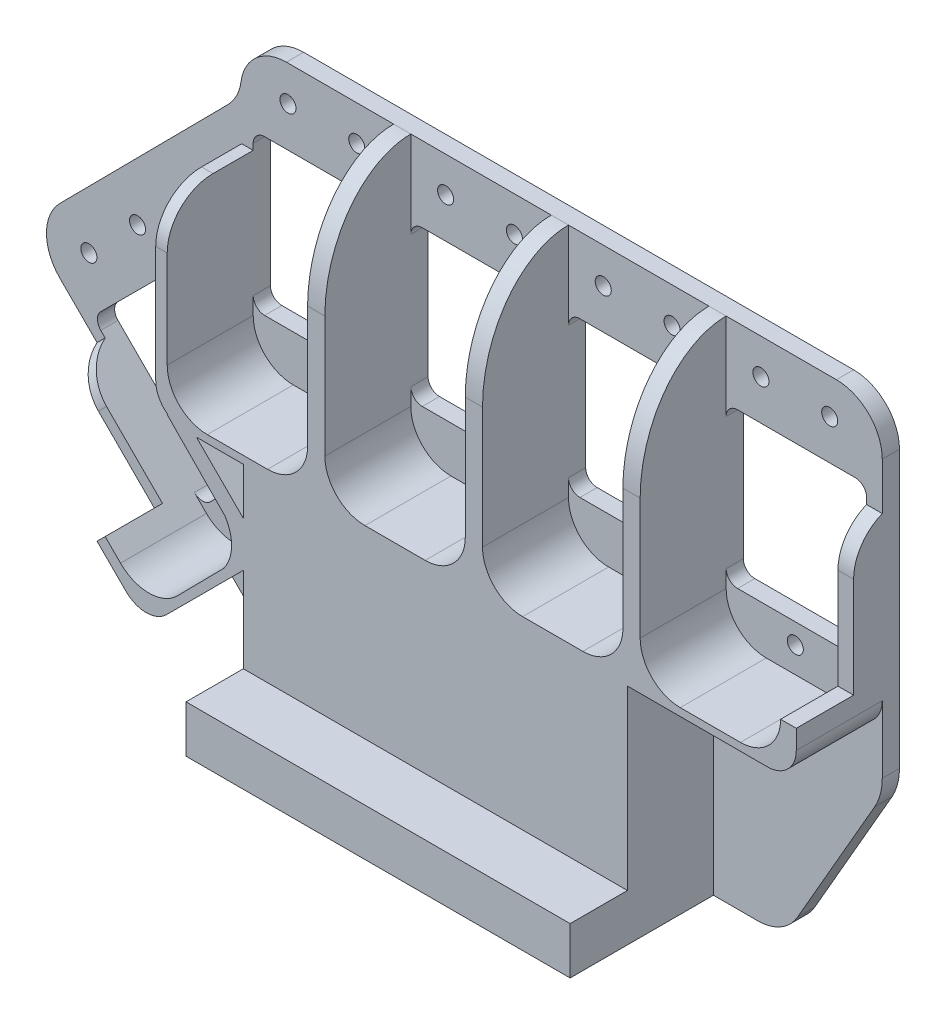
SolidWorks part; units mm, degrees
ref_plane "前视基准面" through (0, 0, 0) normal (0, 0, 1) x (1, 0, 0)
ref_plane "上视基准面" through (0, 0, 0) normal (0, 1, 0) x (1, 0, 0)
ref_plane "右视基准面" through (0, 0, 0) normal (1, 0, 0) x (0, 0, -1)
other "Configuration Table"
sketch "草图2" plane through (0, 0, 0) normal (0, 0, 1) x (1, 0, 0)
  line L0 (151.0633, 209.0132) -> (151.0476, 168.4956)
  line L1 (178.2976, 201.2948) -> (178.2976, 178.2948)
  line L2 (178.2976, 178.2948) -> (178.2976, 175.2948)
  line L3 (206.1919, 197.3972) -> (206.1919, 171.3972)
  line L4 (194.4691, 218.3694) -> (201.3108, 217.5164)
  line L5 (201.3108, 217.5164) -> (208.7441, 216.356)
  line L6 (166.5748, 222.2669) -> (173.4165, 221.4139)
  line L261 (199.1919, 164.3972) -> (192.9419, 164.3972)
  line L262 (237.2256, 158.3592) -> (242.1719, 178.962)
  line L263 (236.0401, 178.625) -> (234.6391, 165.2957)
  line L264 (225.8467, 158.1757) -> (217.3932, 159.0642)
  line L266 (210.2733, 167.8566) -> (212.2453, 186.6193)
  line L267 (252.608, 147.4673) -> (245.8094, 149.0995)
  line L268 (263.7227, 151.9978) -> (271.0421, 182.4855)
  line L269 (188.6919, 164.3972) -> (192.9419, 164.3972)
  line L270 (265.6404, 180.333) -> (245.7068, 185.1186)
  line L271 (252.8645, 197.798) -> (254.0666, 202.8051)
  line L272 (265.506, 196.9076) -> (265.0192, 194.88)
  line L273 (242.1719, 178.962) -> (243.2952, 183.6408)
  line L274 (187.6765, 215.8498) -> (187.692, 213.3583)
  line L275 (200.1917, 213.4362) -> (200.1725, 216.5198)
  line L276 (183.6919, 199.3972) -> (204.1919, 199.3972)
  line L278 (212.2623, 167.6475) -> (232.65, 165.5047)
  line L279 (220.5261, 208.0048) -> (221.0496, 212.986)
  line L280 (235.4723, 192.3568) -> (215.0846, 194.4996)
  line L281 (233.2553, 209.5307) -> (232.9576, 206.6982)
  line L282 (236.0401, 178.625) -> (237.2523, 190.1587)
  line L283 (212.8865, 192.7196) -> (212.2453, 186.6193)
  line L284 (183.6919, 172.3972) -> (204.1919, 172.3972)
  line L285 (239.4038, 158.8646) -> (259.3374, 154.079)
  line L286 (262.7567, 147.974) -> (251.8225, 127.8461)
  line L287 (263.7227, 151.9978) -> (262.7567, 147.974)
  line L288 (181.6919, 197.3972) -> (181.6919, 174.3972)
  line L289 (181.6919, 171.3972) -> (181.6919, 174.3972)
  line L290 (267.1183, 177.9214) -> (261.0487, 152.6398)
  line L291 (171.2976, 168.2948) -> (165.0476, 168.2948)
  line L293 (160.7976, 168.2948) -> (165.0476, 168.2948)
  line L295 (159.7822, 219.7473) -> (159.7977, 217.2558)
  line L296 (172.2974, 217.3337) -> (172.2782, 220.4173)
  line L297 (155.7976, 203.2948) -> (176.2976, 203.2948)
  line L300 (155.7976, 176.2948) -> (176.2976, 176.2948)
  line L301 (153.7976, 201.2948) -> (153.7976, 178.2948)
  line L302 (153.7976, 175.2948) -> (153.7976, 178.2948)
  line L303 (173.4165, 221.4139) -> (194.4691, 218.3694)
  line L304 (187.6765, 215.8498) -> (187.6765, 218.2449)
  line L305 (187.6765, 218.2449) -> (186.8438, 219.4721)
  line L306 (234.2789, 127.8461) -> (251.8225, 127.8461)
  line L307 (233.4789, 133.8446) -> (233.4789, 127.8461)
  line L308 (233.4789, 127.8461) -> (234.2789, 127.8461)
  line L309 (178.4789, 128.6348) -> (178.4789, 135.1402)
  line L310 (172.4789, 127.8461) -> (173.1594, 127.8461)
  line L311 (178.4789, 127.8461) -> (178.4789, 128.6348)
  line L312 (177.6789, 127.8461) -> (178.4789, 127.8461)
  line L313 (173.1594, 127.8461) -> (177.6789, 127.8461)
  line L314 (233.4789, 143.0663) -> (233.4789, 140.4276)
  line L315 (178.4789, 135.1402) -> (178.4789, 139.2823)
  line L316 (178.4789, 139.2823) -> (178.4789, 146.9191)
  line L317 (178.4789, 146.9191) -> (178.4789, 157.8461)
  line L318 (199.0973, 156.1096) -> (218.0428, 154.1184)
  line L319 (181.4789, 160.8461) -> (190.8607, 160.8461)
  line L320 (151.0476, 168.4956) -> (172.4789, 127.8461)
  arc A276 (237.2256, 158.3592) -> (238.6979, 152.1924) centre (244.0322, 156.725) ccw
  arc A277 (210.2733, 167.8566) -> (217.3932, 159.0642) centre (218.2295, 167.0204) ccw
  arc A278 (199.1919, 164.3972) -> (206.1919, 171.3972) centre (199.1919, 171.3972) ccw
  arc A279 (225.8467, 158.1757) -> (234.6391, 165.2957) centre (226.6829, 166.1319) ccw
  arc A281 (242.1719, 178.962) -> (242.2118, 179.1563) centre (239.2548, 179.6624) ccw
  arc A282 (212.2453, 186.6193) -> (212.2566, 186.7575) centre (209.2618, 186.9329) ccw
  arc A283 (236.0666, 178.8175) -> (236.0401, 178.625) centre (239.0236, 178.3114) ccw
  arc A284 (246.0441, 206.6986) -> (242.0035, 208.0676) centre (168.9419, -14.234) ccw
  arc A285 (220.2745, 214.0661) -> (208.7441, 216.356) centre (168.9419, -14.234) ccw
  arc A286 (252.608, 147.4673) -> (261.0487, 152.6398) centre (254.2421, 154.2739) ccw
  arc A287 (181.6919, 171.3972) -> (188.6919, 164.3972) centre (188.6919, 171.3972) ccw
  circle A288 centre (251.4735, 190.9331) radius 1.4
  circle A289 centre (263.142, 188.1317) radius 1.4
  arc A290 (267.1183, 177.9214) -> (265.6404, 180.333) centre (265.1735, 178.3883) ccw
  arc A291 (245.7068, 185.1186) -> (243.2952, 183.6408) centre (245.2399, 183.1739) ccw
  arc A292 (254.0666, 202.8051) -> (253.4554, 203.971) centre (253.0943, 203.0385) ccw
  arc A293 (252.8645, 197.798) -> (265.0192, 194.88) centre (258.9419, 196.339) ccw
  arc A294 (267.1505, 197.4145) -> (265.506, 196.9076) centre (266.4783, 196.6741) ccw
  arc A295 (253.4554, 203.971) -> (246.0441, 206.6986) centre (168.9419, -14.234) ccw
  arc A296 (271.7032, 188.063) -> (267.1505, 197.4145) centre (257.74, 187.0491) ccw
  arc A297 (187.692, 213.3583) -> (200.1917, 213.4362) centre (193.9419, 213.3972) ccw
  arc A298 (201.3108, 217.5164) -> (200.1725, 216.5198) centre (201.1725, 216.526) ccw
  arc A299 (206.1919, 197.3972) -> (204.1919, 199.3972) centre (204.1919, 197.3972) ccw
  arc A300 (183.6919, 199.3972) -> (181.6919, 197.3972) centre (183.6919, 197.3972) ccw
  circle A301 centre (199.9419, 206.3972) radius 1.4
  circle A302 centre (187.9419, 206.3972) radius 1.4
  arc A304 (210.4824, 169.8456) -> (212.2623, 167.6475) centre (212.4714, 169.6366) ccw
  arc A305 (232.65, 165.5047) -> (234.8481, 167.2847) centre (232.8591, 167.4938) ccw
  circle A306 centre (222.0903, 163.0953) radius 1.4
  arc A307 (220.5261, 208.0048) -> (232.9576, 206.6982) centre (226.7419, 207.3515) ccw
  circle A308 centre (220.043, 201.017) radius 1.4
  circle A309 centre (231.9773, 199.7627) radius 1.4
  arc A310 (237.2523, 190.1587) -> (235.4723, 192.3568) centre (235.2632, 190.3678) ccw
  arc A311 (221.0496, 212.986) -> (220.2745, 214.0661) centre (220.0551, 213.0905) ccw
  arc A312 (234.5301, 210.386) -> (233.2553, 209.5307) centre (234.2498, 209.4261) ccw
  arc A313 (215.0846, 194.4996) -> (212.8865, 192.7196) centre (214.8756, 192.5106) ccw
  arc A314 (242.0038, 208.0674) -> (234.5301, 210.386) centre (168.9419, -14.234) ccw
  arc A315 (204.1919, 172.3972) -> (206.1919, 174.3972) centre (204.1919, 174.3972) ccw
  circle A316 centre (193.9419, 168.8972) radius 1.4
  arc A317 (181.6919, 174.3972) -> (183.6919, 172.3972) centre (183.6919, 174.3972) ccw
  arc A318 (259.3374, 154.079) -> (261.749, 155.5569) centre (259.8043, 156.0238) ccw
  arc A319 (237.926, 161.2763) -> (239.4038, 158.8646) centre (239.8707, 160.8094) ccw
  circle A320 centre (248.5535, 153.0685) radius 1.4
  circle A321 centre (193.9419, 213.3972) radius 3.5
  circle A323 centre (258.9419, 196.339) radius 3.5
  arc A324 (263.3908, 199.858) -> (253.4554, 203.971) centre (168.9419, -14.234) ccw
  arc A325 (267.1505, 197.4145) -> (263.3908, 199.858) centre (257.74, 187.0491) ccw
  circle A326 centre (226.7419, 207.3515) radius 3.5
  arc A327 (234.5301, 210.386) -> (220.2745, 214.0661) centre (168.9419, -14.234) ccw
  arc A328 (171.2976, 168.2948) -> (178.2976, 175.2948) centre (171.2976, 175.2948) ccw
  arc A331 (153.7976, 175.2948) -> (160.7976, 168.2948) centre (160.7976, 175.2948) ccw
  arc A332 (159.7822, 219.7473) -> (158.3002, 220.6173) centre (158.7822, 219.7411) ccw
  arc A333 (159.7977, 217.2558) -> (172.2974, 217.3337) centre (166.0476, 217.2948) ccw
  arc A334 (173.4165, 221.4139) -> (172.2782, 220.4173) centre (173.2782, 220.4235) ccw
  arc A335 (178.2976, 201.2948) -> (176.2976, 203.2948) centre (176.2976, 201.2948) ccw
  arc A336 (155.7976, 203.2948) -> (153.7976, 201.2948) centre (155.7976, 201.2948) ccw
  circle A337 centre (172.0476, 210.2948) radius 1.4
  circle A338 centre (160.0476, 210.2948) radius 1.4
  arc A339 (158.3002, 220.6173) -> (152.4939, 214.5477) centre (165.0476, 208.3505) ccw
  arc A340 (176.2976, 176.2948) -> (178.2976, 178.2948) centre (176.2976, 178.2948) ccw
  circle A341 centre (166.0476, 172.7948) radius 1.4
  arc A342 (153.7976, 178.2948) -> (155.7976, 176.2948) centre (155.7976, 178.2948) ccw
  circle A343 centre (166.0476, 217.2948) radius 3.5
  arc A345 (166.5748, 222.2669) -> (158.3002, 220.6173) centre (165.0476, 208.3505) ccw
  arc A346 (220.5415, 152.1792) -> (221.76, 150.0096) centre (228.0411, 154.9641) ccw
  arc A347 (193.3351, 159.5424) -> (199.0973, 156.1096) centre (199.9335, 164.0658) ccw
  arc A348 (220.5415, 152.1792) -> (218.0428, 154.1184) centre (217.7292, 151.1348) ccw
  arc A349 (193.3351, 159.5424) -> (190.8607, 160.8461) centre (190.8607, 157.8461) ccw
  arc A350 (181.4789, 160.8461) -> (178.4789, 157.8461) centre (181.4789, 157.8461) ccw
  spline S5 degree 3 poles (245.8094, 149.0995) (244.7023, 149.3653) (243.562, 149.639) (242.3981, 149.9185) knots 0 0 0 0 1 1 1 1
  spline S6 degree 3 poles (242.3981, 149.9185) (240.9661, 150.2604) (239.6561, 151.0615) (238.6979, 152.1924) knots 0 0 0 0 1 1 1 1
  spline S7 degree 3 poles (271.0421, 182.4855) (271.1468, 182.9215) (271.2515, 183.3575) (271.3531, 183.7809) knots 0 0 0 0 1 1 1 1
  spline S8 degree 3 poles (271.3531, 183.7809) (271.6392, 184.9581) (271.73, 186.0745) (271.7435, 187.2429) (271.7328, 187.5457) (271.7129, 187.9558) (271.7023, 188.0633) (271.7026, 188.063) knots 0 0 0 0 0.5 0.5 0.75 0.75 1 1 1 1
  spline S9 degree 3 poles (152.4939, 214.5476) (152.4935, 214.5473) (152.4251, 214.4133) (152.183, 213.882) (152.0119, 213.4848) (151.6571, 212.4716) (151.4748, 211.8536) (151.1955, 210.4931) (151.098, 209.7566) (151.0633, 209.0132) knots 0 0 0 0 0.25 0.25 0.5 0.5 0.75 0.75 1 1 1 1
  spline S10 degree 3 poles (233.4789, 140.4276) (233.4789, 138.7088) (233.4789, 136.2853) (233.4789, 133.8446) knots 0 0 0 0 1 1 1 1
  spline S11 degree 3 poles (233.2337, 144.2542) (233.3952, 143.8804) (233.4792, 143.4735) (233.4789, 143.0663) knots 0 0 0 0 1 1 1 1
  spline S12 degree 3 poles (231.1793, 145.9834) (231.6902, 145.8625) (232.1463, 145.6054) (232.8415, 144.9724) (233.0819, 144.6067) (233.2337, 144.2542) knots 0 0 0 0 0.5 0.5 1 1 1 1
  spline S13 degree 3 poles (226.1736, 147.1852) (227.9043, 146.7697) (229.5835, 146.3665) (231.1793, 145.9834) knots 0 0 0 0 1 1 1 1
  spline S14 degree 3 poles (221.76, 150.0096) (222.8696, 148.5987) (224.4447, 147.5969) (226.1736, 147.1852) knots 0 0 0 0 1 1 1 1
  line B0 (187.9419, 206.3972) -> (187.9419, 208.8972)
  line B1 (187.9419, 206.3972) -> (185.4419, 206.3972)
  line B2 (187.9419, 206.3972) -> (187.9419, 203.8972)
  line B3 (187.9419, 206.3972) -> (190.4419, 206.3972)
  line B4 (187.9419, 208.8972) -> (187.9419, 210.2972)
  line B5 (185.4419, 206.3972) -> (184.0419, 206.3972)
  line B6 (187.9419, 203.8972) -> (187.9419, 202.4972)
  line B7 (190.4419, 206.3972) -> (191.8419, 206.3972)
  line B8 (222.0903, 163.0953) -> (222.0903, 165.5953)
  line B9 (222.0903, 163.0953) -> (219.5903, 163.0953)
  line B10 (222.0903, 163.0953) -> (222.0903, 160.5953)
  line B11 (222.0903, 163.0953) -> (224.5903, 163.0953)
  line B12 (222.0903, 165.5953) -> (222.0903, 166.9953)
  line B13 (219.5903, 163.0953) -> (218.1903, 163.0953)
  line B14 (222.0903, 160.5953) -> (222.0903, 159.1953)
  line B15 (224.5903, 163.0953) -> (225.9903, 163.0953)
  line B16 (251.4735, 190.9331) -> (251.4735, 193.4331)
  line B17 (251.4735, 190.9331) -> (248.9735, 190.9331)
  line B18 (251.4735, 190.9331) -> (251.4735, 188.4331)
  line B19 (251.4735, 190.9331) -> (253.9735, 190.9331)
  line B20 (251.4735, 193.4331) -> (251.4735, 194.8331)
  line B21 (248.9735, 190.9331) -> (247.5735, 190.9331)
  line B22 (251.4735, 188.4331) -> (251.4735, 187.0331)
  line B23 (253.9735, 190.9331) -> (255.3735, 190.9331)
  line B24 (263.142, 188.1317) -> (263.142, 190.6317)
  line B25 (263.142, 188.1317) -> (260.642, 188.1317)
  line B26 (263.142, 188.1317) -> (263.142, 185.6317)
  line B27 (263.142, 188.1317) -> (265.642, 188.1317)
  line B28 (263.142, 190.6317) -> (263.142, 192.0317)
  line B29 (260.642, 188.1317) -> (259.242, 188.1317)
  line B30 (263.142, 185.6317) -> (263.142, 184.2317)
  line B31 (265.642, 188.1317) -> (267.042, 188.1317)
  line B32 (248.5535, 153.0685) -> (248.5535, 155.5685)
  line B33 (248.5535, 153.0685) -> (246.0535, 153.0685)
  line B34 (248.5535, 153.0685) -> (248.5535, 150.5685)
  line B35 (248.5535, 153.0685) -> (251.0535, 153.0685)
  line B36 (248.5535, 155.5685) -> (248.5535, 156.9685)
  line B37 (246.0535, 153.0685) -> (244.6535, 153.0685)
  line B38 (248.5535, 150.5685) -> (248.5535, 149.1685)
  line B39 (251.0535, 153.0685) -> (252.4535, 153.0685)
  line B40 (231.9773, 199.7627) -> (231.9773, 202.2627)
  line B41 (231.9773, 199.7627) -> (229.4773, 199.7627)
  line B42 (231.9773, 199.7627) -> (231.9773, 197.2627)
  line B43 (231.9773, 199.7627) -> (234.4773, 199.7627)
  line B44 (231.9773, 202.2627) -> (231.9773, 203.6627)
  line B45 (229.4773, 199.7627) -> (228.0773, 199.7627)
  line B46 (231.9773, 197.2627) -> (231.9773, 195.8627)
  line B47 (234.4773, 199.7627) -> (235.8773, 199.7627)
  line B48 (220.043, 201.017) -> (220.043, 203.517)
  line B49 (220.043, 201.017) -> (217.543, 201.017)
  line B50 (220.043, 201.017) -> (220.043, 198.517)
  line B51 (220.043, 201.017) -> (222.543, 201.017)
  line B52 (220.043, 203.517) -> (220.043, 204.917)
  line B53 (217.543, 201.017) -> (216.143, 201.017)
  line B54 (220.043, 198.517) -> (220.043, 197.117)
  line B55 (222.543, 201.017) -> (223.943, 201.017)
  line B56 (193.9419, 168.8972) -> (193.9419, 171.3972)
  line B57 (193.9419, 168.8972) -> (191.4419, 168.8972)
  line B58 (193.9419, 168.8972) -> (193.9419, 166.3972)
  line B59 (193.9419, 168.8972) -> (196.4419, 168.8972)
  line B60 (193.9419, 171.3972) -> (193.9419, 172.7972)
  line B61 (191.4419, 168.8972) -> (190.0419, 168.8972)
  line B62 (193.9419, 166.3972) -> (193.9419, 164.9972)
  line B63 (196.4419, 168.8972) -> (197.8419, 168.8972)
  line B64 (199.9419, 206.3972) -> (199.9419, 208.8972)
  line B65 (199.9419, 206.3972) -> (197.4419, 206.3972)
  line B66 (199.9419, 206.3972) -> (199.9419, 203.8972)
  line B67 (199.9419, 206.3972) -> (202.4419, 206.3972)
  line B68 (199.9419, 208.8972) -> (199.9419, 210.2972)
  line B69 (197.4419, 206.3972) -> (196.0419, 206.3972)
  line B70 (199.9419, 203.8972) -> (199.9419, 202.4972)
  line B71 (202.4419, 206.3972) -> (203.8419, 206.3972)
  line B72 (160.0476, 210.2948) -> (160.0476, 212.7948)
  line B73 (160.0476, 210.2948) -> (157.5476, 210.2948)
  line B74 (160.0476, 210.2948) -> (160.0476, 207.7948)
  line B75 (160.0476, 210.2948) -> (162.5476, 210.2948)
  line B76 (160.0476, 212.7948) -> (160.0476, 214.1948)
  line B77 (157.5476, 210.2948) -> (156.1476, 210.2948)
  line B78 (160.0476, 207.7948) -> (160.0476, 206.3948)
  line B79 (162.5476, 210.2948) -> (163.9476, 210.2948)
  line B80 (166.0476, 172.7948) -> (166.0476, 175.2948)
  line B81 (166.0476, 172.7948) -> (163.5476, 172.7948)
  line B82 (166.0476, 172.7948) -> (166.0476, 170.2948)
  line B83 (166.0476, 172.7948) -> (168.5476, 172.7948)
  line B84 (166.0476, 175.2948) -> (166.0476, 176.6948)
  line B85 (163.5476, 172.7948) -> (162.1476, 172.7948)
  line B86 (166.0476, 170.2948) -> (166.0476, 168.8948)
  line B87 (168.5476, 172.7948) -> (169.9476, 172.7948)
  line B88 (172.0476, 210.2948) -> (172.0476, 212.7948)
  line B89 (172.0476, 210.2948) -> (169.5476, 210.2948)
  line B90 (172.0476, 210.2948) -> (172.0476, 207.7948)
  line B91 (172.0476, 210.2948) -> (174.5476, 210.2948)
  line B92 (172.0476, 212.7948) -> (172.0476, 214.1948)
  line B93 (169.5476, 210.2948) -> (168.1476, 210.2948)
  line B94 (172.0476, 207.7948) -> (172.0476, 206.3948)
  line B95 (174.5476, 210.2948) -> (175.9476, 210.2948)
sketch_block_instance "SW_CENTERMARKSYMBOL_3-1"
sketch_block "SW_CENTERMARKSYMBOL_3"
sketch_block_instance "SW_CENTERMARKSYMBOL_4-1"
sketch_block "SW_CENTERMARKSYMBOL_4"
sketch_block_instance "SW_CENTERMARKSYMBOL_5-1"
sketch_block "SW_CENTERMARKSYMBOL_5"
sketch_block_instance "SW_CENTERMARKSYMBOL_6-1"
sketch_block "SW_CENTERMARKSYMBOL_6"
sketch_block_instance "SW_CENTERMARKSYMBOL_7-1"
sketch_block "SW_CENTERMARKSYMBOL_7"
sketch_block_instance "SW_CENTERMARKSYMBOL_8-1"
sketch_block "SW_CENTERMARKSYMBOL_8"
sketch_block_instance "SW_CENTERMARKSYMBOL_9-1"
sketch_block "SW_CENTERMARKSYMBOL_9"
sketch_block_instance "SW_CENTERMARKSYMBOL_10-1"
sketch_block "SW_CENTERMARKSYMBOL_10"
sketch_block_instance "SW_CENTERMARKSYMBOL_11-1"
sketch_block "SW_CENTERMARKSYMBOL_11"
sketch_block_instance "SW_CENTERMARKSYMBOL_3-2"
sketch_block_instance "SW_CENTERMARKSYMBOL_10-2"
sketch_block_instance "SW_CENTERMARKSYMBOL_11-2"
ref_plane "基准面2" through (0, 0, 15.8251) normal (0, 0, 1) x (1, 0, 0)
sketch "草图12" plane through (0, 0, 15.8251) normal (0, 0, 1) x (1, 0, 0)
  line L2 (157.1388, 216.4507) -> (268.9252, 216.4507)
  line L5 (268.9252, 216.4507) -> (268.9252, 157.5622)
  line L9 (251.8225, 127.8461) -> (233.4789, 127.8461)
  line L10 (233.4789, 127.8461) -> (233.4789, 143.0663)
  line L12 (178.4789, 127.8461) -> (178.4789, 157.8461)
  line L13 (181.4789, 160.8461) -> (190.8607, 160.8461)
  line L14 (199.0973, 156.1096) -> (218.0428, 154.1184)
  line L15 (226.1736, 147.1852) -> (231.1793, 145.9834)
  line L23 (188.6945, 203.2948) -> (209.1945, 203.2948)
  line L24 (211.1945, 201.2948) -> (211.1945, 178.2948)
  line L25 (209.1945, 176.2948) -> (188.6945, 176.2948)
  line L26 (186.6945, 178.2948) -> (186.6945, 201.2948)
  line L27 (186.6945, 178.2948) -> (186.6945, 175.2948)
  line L28 (211.1945, 178.2948) -> (211.1945, 175.2948)
  line L29 (193.6945, 168.2948) -> (204.1945, 168.2948)
  line L30 (268.9252, 157.5622) -> (251.8225, 127.8461)
  line L51 (216.1945, 203.2948) -> (236.6945, 203.2948)
  line L52 (238.6945, 201.2948) -> (238.6945, 178.2948)
  line L53 (236.6945, 176.2948) -> (216.1945, 176.2948)
  line L54 (214.1945, 178.2948) -> (214.1945, 201.2948)
  line L55 (214.1945, 178.2948) -> (214.1945, 175.2948)
  line L56 (238.6945, 178.2948) -> (238.6945, 175.2948)
  line L57 (221.1945, 168.2948) -> (231.6945, 168.2948)
  line L60 (161.1945, 203.2948) -> (181.6945, 203.2948)
  line L61 (183.6945, 201.2948) -> (183.6945, 178.2948)
  line L62 (181.6945, 176.2948) -> (161.1945, 176.2948)
  line L63 (159.1945, 178.2948) -> (159.1945, 201.2948)
  line L64 (159.1945, 178.2948) -> (159.1945, 175.2948)
  line L65 (183.6945, 178.2948) -> (183.6945, 175.2948)
  line L66 (166.1945, 168.2948) -> (176.6945, 168.2948)
  line L69 (238.6945, 201.2948) -> (238.6945, 178.2948)
  line L70 (238.6945, 178.2948) -> (238.6945, 175.2948)
  line L72 (243.6945, 203.2948) -> (264.1945, 203.2948)
  line L73 (265.8853, 200.2265) -> (265.8853, 179.3631)
  line L74 (264.1945, 176.2948) -> (243.6945, 176.2948)
  line L75 (241.6945, 178.2948) -> (241.6945, 201.2948)
  line L76 (241.6945, 178.2948) -> (241.6945, 175.2948)
  line L77 (265.8853, 179.3631) -> (265.8853, 175.1696)
  line L78 (248.6945, 168.2948) -> (259.1917, 168.2948)
  line L83 (325.7181, 277.8251) -> (346.2181, 277.8251)
  line L84 (348.2181, 275.8251) -> (348.2181, 252.8251)
  line L85 (346.2181, 250.8251) -> (325.7181, 250.8251)
  line L86 (323.7181, 252.8251) -> (323.7181, 275.8251)
  line L87 (323.7181, 252.8251) -> (323.7181, 249.8251)
  line L88 (348.2181, 252.8251) -> (348.2181, 249.8251)
  line L89 (330.7181, 242.8251) -> (341.2181, 242.8251)
  line L91 (352.2181, 277.8251) -> (372.7181, 277.8251)
  line L92 (374.7181, 275.8251) -> (374.7181, 252.8251)
  line L93 (372.7181, 250.8251) -> (352.2181, 250.8251)
  line L94 (350.2181, 252.8251) -> (350.2181, 275.8251)
  line L95 (350.2181, 252.8251) -> (350.2181, 249.8251)
  line L96 (374.7181, 252.8251) -> (374.7181, 249.8251)
  line L97 (357.2181, 242.8251) -> (367.7181, 242.8251)
  line L98 (299.404, 277.8251) -> (319.904, 277.8251)
  line L100 (319.904, 250.8251) -> (299.404, 250.8251)
  line L101 (159.6321, 140.0993) -> (169.0726, 149.5397)
  line L102 (297.404, 252.8251) -> (297.404, 249.8251)
  line L103 (321.904, 252.8251) -> (321.904, 249.8251)
  line L104 (304.404, 242.8251) -> (314.904, 242.8251)
  line L106 (374.7181, 275.8251) -> (374.7181, 252.8251)
  line L107 (374.7181, 252.8251) -> (374.7181, 249.8251)
  line L108 (378.7181, 277.8251) -> (399.2181, 277.8251)
  line L109 (401.2181, 275.8251) -> (401.2181, 252.8251)
  line L110 (399.2181, 250.8251) -> (378.7181, 250.8251)
  line L111 (376.7181, 252.8251) -> (376.7181, 275.8251)
  line L112 (376.7181, 252.8251) -> (376.7181, 249.8251)
  line L113 (401.2181, 252.8251) -> (401.2181, 249.8251)
  line L114 (383.7181, 242.8251) -> (394.2181, 242.8251)
  line L115 (166.1991, 157.98) -> (151.7034, 143.4843)
  line L117 (132.6116, 162.5762) -> (147.1073, 177.0719)
  line L118 (149.9357, 177.0719) -> (166.1991, 160.8084)
  line L121 (119.8478, 169.6832) -> (161.6848, 127.8461)
  line L122 (161.6848, 127.8461) -> (178.4789, 127.8461)
  line L124 (151.0538, 141.3055) -> (132.6116, 159.7478)
  line L126 (157.1388, 207.3145) -> (157.1388, 216.4507)
  line L129 (168.3779, 158.6297) -> (166.1991, 160.8084)
  line L130 (154.0169, 144.2791) -> (154.0432, 144.2528)
  line L131 (119.8478, 169.6832) -> (157.1388, 207.3145)
  line L132 (150.158, 176.8496) -> (168.6067, 158.4009)
  arc A4 (181.4789, 160.8461) -> (178.4789, 157.8461) centre (181.4789, 157.8461) ccw
  arc A8 (193.3351, 159.5424) -> (190.8607, 160.8461) centre (190.8607, 157.8461) ccw
  arc A9 (193.3351, 159.5424) -> (199.0973, 156.1096) centre (199.9335, 164.0658) ccw
  arc A10 (220.5415, 152.1792) -> (218.0428, 154.1184) centre (217.7292, 151.1348) ccw
  arc A11 (220.5415, 152.1792) -> (226.1736, 147.1852) centre (228.0411, 154.9641) ccw
  arc A28 (188.6945, 203.2948) -> (186.6945, 201.2948) centre (188.6945, 201.2948) ccw
  arc A30 (211.1945, 201.2948) -> (209.1945, 203.2948) centre (209.1945, 201.2948) ccw
  arc A31 (186.6945, 178.2948) -> (188.6945, 176.2948) centre (188.6945, 178.2948) ccw
  arc A32 (209.1945, 176.2948) -> (211.1945, 178.2948) centre (209.1945, 178.2948) ccw
  arc A34 (186.6945, 175.2948) -> (193.6945, 168.2948) centre (193.6945, 175.2948) ccw
  arc A35 (204.1945, 168.2948) -> (211.1945, 175.2948) centre (204.1945, 175.2948) ccw
  arc A53 (216.1945, 203.2948) -> (214.1945, 201.2948) centre (216.1945, 201.2948) ccw
  arc A54 (238.6945, 201.2948) -> (236.6945, 203.2948) centre (236.6945, 201.2948) ccw
  arc A55 (214.1945, 178.2948) -> (216.1945, 176.2948) centre (216.1945, 178.2948) ccw
  arc A56 (236.6945, 176.2948) -> (238.6945, 178.2948) centre (236.6945, 178.2948) ccw
  arc A58 (214.1945, 175.2948) -> (221.1945, 168.2948) centre (221.1945, 175.2948) ccw
  arc A59 (231.6945, 168.2948) -> (238.6945, 175.2948) centre (231.6945, 175.2948) ccw
  arc A60 (161.1945, 203.2948) -> (159.1945, 201.2948) centre (161.1945, 201.2948) ccw
  arc A61 (183.6945, 201.2948) -> (181.6945, 203.2948) centre (181.6945, 201.2948) ccw
  arc A62 (159.1945, 178.2948) -> (161.1945, 176.2948) centre (161.1945, 178.2948) ccw
  arc A63 (181.6945, 176.2948) -> (183.6945, 178.2948) centre (181.6945, 178.2948) ccw
  circle A64 centre (171.2586, 172.7948) radius 1.4
  arc A65 (159.1945, 175.2948) -> (166.1945, 168.2948) centre (166.1945, 175.2948) ccw
  arc A66 (176.6945, 168.2948) -> (183.6945, 175.2948) centre (176.6945, 175.2948) ccw
  arc A69 (243.6945, 203.2948) -> (241.6945, 201.2948) centre (243.6945, 201.2948) ccw
  arc A70 (265.8853, 200.2265) -> (264.1945, 203.2948) centre (264.1945, 201.2948) ccw
  arc A71 (241.6945, 178.2948) -> (243.6945, 176.2948) centre (243.6945, 178.2948) ccw
  arc A72 (264.1945, 176.2948) -> (265.8853, 179.3631) centre (264.1945, 178.2948) ccw
  arc A74 (241.6945, 175.2948) -> (248.6945, 168.2948) centre (248.6945, 175.2948) ccw
  arc A75 (259.1917, 168.2948) -> (265.8853, 175.1696) centre (259.008, 175.1696) ccw
  circle A76 centre (165.2586, 210.2948) radius 1.4
  circle A77 centre (177.2586, 210.2948) radius 1.4
  arc A85 (325.7181, 277.8251) -> (323.7181, 275.8251) centre (325.7181, 275.8251) ccw
  arc A86 (348.2181, 275.8251) -> (346.2181, 277.8251) centre (346.2181, 275.8251) ccw
  arc A87 (323.7181, 252.8251) -> (325.7181, 250.8251) centre (325.7181, 252.8251) ccw
  arc A88 (346.2181, 250.8251) -> (348.2181, 252.8251) centre (346.2181, 252.8251) ccw
  circle A89 centre (335.9681, 247.3251) radius 1.4
  arc A90 (323.7181, 249.8251) -> (330.7181, 242.8251) centre (330.7181, 249.8251) ccw
  arc A91 (341.2181, 242.8251) -> (348.2181, 249.8251) centre (341.2181, 249.8251) ccw
  arc A94 (352.2181, 277.8251) -> (350.2181, 275.8251) centre (352.2181, 275.8251) ccw
  arc A95 (374.7181, 275.8251) -> (372.7181, 277.8251) centre (372.7181, 275.8251) ccw
  arc A96 (350.2181, 252.8251) -> (352.2181, 250.8251) centre (352.2181, 252.8251) ccw
  arc A97 (372.7181, 250.8251) -> (374.7181, 252.8251) centre (372.7181, 252.8251) ccw
  circle A98 centre (362.4681, 247.3251) radius 1.4
  arc A99 (350.2181, 249.8251) -> (357.2181, 242.8251) centre (357.2181, 249.8251) ccw
  arc A100 (367.7181, 242.8251) -> (374.7181, 249.8251) centre (367.7181, 249.8251) ccw
  arc A101 (299.404, 277.8251) -> (297.404, 275.8251) centre (299.404, 275.8251) ccw
  arc A102 (321.904, 275.8251) -> (319.904, 277.8251) centre (319.904, 275.8251) ccw
  arc A103 (297.404, 252.8251) -> (299.404, 250.8251) centre (299.404, 252.8251) ccw
  arc A104 (319.904, 250.8251) -> (321.904, 252.8251) centre (319.904, 252.8251) ccw
  circle A105 centre (309.4681, 247.3251) radius 1.4
  arc A106 (297.404, 249.8251) -> (304.404, 242.8251) centre (304.404, 249.8251) ccw
  arc A107 (314.904, 242.8251) -> (321.904, 249.8251) centre (314.904, 249.8251) ccw
  arc A110 (378.7181, 277.8251) -> (376.7181, 275.8251) centre (378.7181, 275.8251) ccw
  arc A111 (401.2181, 275.8251) -> (399.2181, 277.8251) centre (399.2181, 275.8251) ccw
  arc A112 (376.7181, 252.8251) -> (378.7181, 250.8251) centre (378.7181, 252.8251) ccw
  arc A113 (399.2181, 250.8251) -> (401.2181, 252.8251) centre (399.2181, 252.8251) ccw
  circle A114 centre (388.9681, 247.3251) radius 1.4
  arc A115 (376.7181, 249.8251) -> (383.7181, 242.8251) centre (383.7181, 249.8251) ccw
  arc A116 (394.2181, 242.8251) -> (401.2181, 249.8251) centre (394.2181, 249.8251) ccw
  circle A117 centre (204.7586, 210.2948) radius 1.4
  circle A118 centre (192.7586, 210.2948) radius 1.4
  circle A119 centre (232.2586, 210.2948) radius 1.4
  circle A120 centre (220.2586, 210.2948) radius 1.4
  circle A121 centre (259.7586, 210.2948) radius 1.4
  circle A122 centre (247.7586, 210.2948) radius 1.4
  circle A123 centre (198.7586, 172.7948) radius 1.4
  circle A124 centre (226.2586, 172.7948) radius 1.4
  circle A125 centre (253.7586, 172.7948) radius 1.4
  circle A126 centre (139.0208, 178.885) radius 1.4
  arc A127 (132.6116, 162.5762) -> (132.6116, 159.7478) centre (134.0258, 161.162) ccw
  arc A128 (149.9357, 177.0719) -> (147.1073, 177.0719) centre (148.5215, 175.6577) ccw
  circle A130 centre (161.2947, 148.1258) radius 1.4
  circle A131 centre (130.5356, 170.3997) radius 1.4
  arc A134 (166.1991, 157.98) -> (166.1991, 160.8084) centre (164.7849, 159.3942) ccw
  arc A135 (151.7034, 143.4843) -> (148.875, 143.4843) centre (150.2892, 144.8985) cw
  arc A138 (151.0538, 141.3055) -> (159.6321, 140.0993) centre (156.1435, 146.3952) ccw
  arc A139 (169.0726, 149.5397) -> (168.3779, 158.6297) centre (163.4282, 153.6799) ccw
  spline S1 degree 2 poles (231.1793, 145.9834) (233.4263, 145.1786) (233.4789, 143.0663) knots 0 0 0 1 1 1
  dimension "D6" = 2
  dimension "D1" = 3
  dimension "D2" = 3
  dimension "D3" = 24.5
  dimension "D4" = 3
  dimension "D5" = 3.04
extrude "凸台-拉伸1" add sketch "草图12" along normal blind 3 contours L15 S1 L10 L9 L30 L5 L2 L12 A4 L13 A8 A9 L14 A10 A11 A35 L29 A34 L27 L26 A28 L23 A30 L24 L28 A59 L57 A58 L55 L54 A53 L51 A54 L52 L56 A66 L66 region at (213.032, 214.7165, 15.8251)
sketch "草图23" plane through (0, 0, 18.8251) normal (0, 0, 1) x (1, 0, 0)
  line L0 (181.6945, 176.2948) -> (161.1945, 176.2948)
  line L1 (159.1945, 178.2948) -> (159.1945, 175.2948)
  line L2 (183.6945, 178.2948) -> (183.6945, 175.2948)
  line L3 (166.1945, 168.2948) -> (176.6945, 168.2948)
  line L4 (186.6945, 201.2948) -> (186.6945, 175.2948) construction
  line L5 (264.1945, 176.2948) -> (243.6945, 176.2948)
  line L6 (214.1945, 201.2948) -> (214.1945, 175.2948) construction
  line L7 (241.6945, 201.2948) -> (241.6945, 175.2948) construction
  line L11 (209.1945, 176.2948) -> (188.6945, 176.2948)
  line L12 (186.6945, 178.2948) -> (186.6945, 175.2948)
  line L13 (211.1945, 178.2948) -> (211.1945, 175.2948)
  line L14 (193.6945, 168.2948) -> (204.1945, 168.2948)
  line L15 (236.6945, 176.2948) -> (216.1945, 176.2948)
  line L16 (214.1945, 178.2948) -> (214.1945, 175.2948)
  line L17 (238.6945, 178.2948) -> (238.6945, 175.2948)
  line L18 (221.1945, 168.2948) -> (231.6945, 168.2948)
  line L19 (241.6945, 178.2948) -> (241.6945, 175.2948)
  line L20 (266.1945, 178.2948) -> (266.1945, 175.2948)
  line L21 (248.6945, 168.2948) -> (259.1945, 168.2948)
  arc A0 (159.1945, 178.2948) -> (161.1945, 176.2948) centre (161.1945, 178.2948) ccw
  arc A1 (181.6945, 176.2948) -> (183.6945, 178.2948) centre (181.6945, 178.2948) ccw
  circle A2 centre (171.2586, 172.7948) radius 1.4
  arc A3 (159.1945, 175.2948) -> (166.1945, 168.2948) centre (166.1945, 175.2948) ccw
  arc A4 (176.6945, 168.2948) -> (183.6945, 175.2948) centre (176.6945, 175.2948) ccw
  arc A5 (186.6945, 178.2948) -> (188.6945, 176.2948) centre (188.6945, 178.2948) ccw
  arc A6 (209.1945, 176.2948) -> (211.1945, 178.2948) centre (209.1945, 178.2948) ccw
  circle A7 centre (198.7586, 172.7948) radius 1.4
  arc A8 (186.6945, 175.2948) -> (193.6945, 168.2948) centre (193.6945, 175.2948) ccw
  arc A9 (204.1945, 168.2948) -> (211.1945, 175.2948) centre (204.1945, 175.2948) ccw
  arc A10 (214.1945, 178.2948) -> (216.1945, 176.2948) centre (216.1945, 178.2948) ccw
  arc A11 (236.6945, 176.2948) -> (238.6945, 178.2948) centre (236.6945, 178.2948) ccw
  circle A12 centre (226.2586, 172.7948) radius 1.4
  arc A13 (214.1945, 175.2948) -> (221.1945, 168.2948) centre (221.1945, 175.2948) ccw
  arc A14 (231.6945, 168.2948) -> (238.6945, 175.2948) centre (231.6945, 175.2948) ccw
  arc A15 (241.6945, 178.2948) -> (243.6945, 176.2948) centre (243.6945, 178.2948) ccw
  arc A16 (264.1945, 176.2948) -> (266.1945, 178.2948) centre (264.1945, 178.2948) ccw
  circle A17 centre (253.7586, 172.7948) radius 1.4
  arc A18 (241.6945, 175.2948) -> (248.6945, 168.2948) centre (248.6945, 175.2948) ccw
  arc A19 (259.1945, 168.2948) -> (266.1945, 175.2948) centre (259.1945, 175.2948) ccw
extrude "凸台-拉伸2" add sketch "草图23" against normal blind 3
sketch "草图24" plane through (0, 0, 18.8251) normal (0, 0, 1) x (1, 0, 0)
  line L0 (157.1945, 213.2289) -> (157.1945, 156.8365) construction
  line L1 (157.1945, 200.2299) -> (159.1945, 200.2299)
  line L2 (157.1945, 200.2299) -> (157.1945, 166.9524)
  line L4 (159.1945, 200.2299) -> (159.1945, 175.2948)
  line L5 (193.6945, 168.2948) -> (204.1945, 168.2948)
  line L6 (268.9252, 216.4507) -> (268.9252, 157.5622) construction
  line L9 (268.9252, 200.2299) -> (266.1945, 200.2299)
  line L10 (268.9252, 200.2299) -> (268.9252, 166.9524)
  line L12 (266.1945, 200.2299) -> (266.1945, 175.2948)
  line L14 (183.6945, 216.4507) -> (186.6945, 216.4507)
  line L16 (157.1388, 216.4507) -> (268.9252, 216.4507) construction
  line L19 (211.1945, 216.4507) -> (211.1945, 175.2948)
  line L21 (214.1945, 216.4507) -> (214.1945, 175.2948)
  line L22 (241.6945, 216.4507) -> (241.6945, 178.2948)
  line L23 (211.1945, 216.4507) -> (214.1945, 216.4507)
  line L24 (159.1945, 178.2948) -> (159.1945, 175.2948)
  line L26 (238.6945, 216.4507) -> (238.6945, 175.2948)
  line L28 (241.6945, 216.4507) -> (241.6945, 175.2948)
  line L29 (238.6945, 216.4507) -> (241.6945, 216.4507)
  line L30 (166.1945, 168.2948) -> (176.6945, 168.2948)
  line L35 (183.6945, 178.2948) -> (183.6945, 175.2948)
  line L36 (166.1945, 168.2948) -> (176.6945, 168.2948)
  line L38 (186.6945, 178.2948) -> (186.6945, 175.2948)
  line L43 (211.1945, 178.2948) -> (211.1945, 175.2948)
  line L46 (214.1945, 178.2948) -> (214.1945, 175.2948)
  line L47 (238.6945, 178.2948) -> (238.6945, 175.2948)
  line L50 (241.6945, 178.2948) -> (241.6945, 175.2948)
  line L51 (266.1945, 178.2948) -> (266.1945, 175.2948)
  line L52 (248.6945, 168.2948) -> (259.1945, 168.2948)
  line L55 (159.1945, 200.2299) -> (159.1945, 178.2948)
  line L56 (183.6945, 175.2948) -> (183.6945, 216.4507)
  line L57 (186.6945, 175.2948) -> (186.6945, 216.4507)
  line L58 (268.9252, 166.9524) -> (157.1945, 166.9524)
  line L60 (248.6945, 168.2948) -> (259.1945, 168.2948)
  line L61 (266.1945, 200.2299) -> (266.1945, 178.2948)
  line L62 (221.1945, 168.2948) -> (231.6945, 168.2948)
  circle A7 centre (171.2586, 172.7948) radius 1.4
  arc A8 (159.1945, 175.2948) -> (166.1945, 168.2948) centre (166.1945, 175.2948) ccw
  arc A9 (176.6945, 168.2948) -> (183.6945, 175.2948) centre (176.6945, 175.2948) ccw
  circle A17 centre (198.7586, 172.7948) radius 1.4
  circle A22 centre (226.2586, 172.7948) radius 1.4
  circle A27 centre (253.7586, 172.7948) radius 1.4
  arc A28 (241.6945, 175.2948) -> (248.6945, 168.2948) centre (248.6945, 175.2948) ccw
  arc A29 (259.1945, 168.2948) -> (266.1945, 175.2948) centre (259.1945, 175.2948) ccw
  arc A30 (186.6945, 175.2948) -> (193.6945, 168.2948) centre (193.6945, 175.2948) ccw
  arc A31 (204.1945, 168.2948) -> (211.1945, 175.2948) centre (204.1945, 175.2948) ccw
  arc A32 (214.1945, 175.2948) -> (221.1945, 168.2948) centre (221.1945, 175.2948) ccw
  arc A33 (231.6945, 168.2948) -> (238.6945, 175.2948) centre (231.6945, 175.2948) ccw
  dimension "D1" = 3
  dimension "D2" = 3
  dimension "D3" = 24.5
  dimension "D4" = 24.5
  dimension "D5" = 3
  dimension "D6" = 24.5
extrude "凸台-拉伸3" add sketch "草图24" along normal blind 15 contours A29 L52 A28 L28 L29 L26 L21 L23 L19 L38 L57 L14 L56 L35 A9 L30 A8 L4 L1 L2 L58 L10 L9 L12 region at (158.1945, 199.0078, 18.8251)
fillet "圆角3" radius 10 1 edges at (268.9252, 157.5622, 17.3251)
fillet "圆角4" radius 20 3 edges at (240.1945, 216.4507, 33.8251) (212.6945, 216.4507, 33.8251) (185.1945, 216.4507, 33.8251) second distance 15 first distance on face at (212.7467, 184.666, 33.8251)
fillet "圆角6" radius 5 2 edges at (268.9252, 166.9524, 26.3251) (157.1945, 166.9524, 26.3251)
sketch "草图28" plane through (0, 0, 18.8251) normal (0, 0, 1) x (1, 0, 0)
sketch "草图29" plane through (0, 0, 18.8251) normal (0, 0, 1) x (1, 0, 0)
  line L0 (159.0741, 137.5279) -> (176.3982, 154.852)
  line L15 (159.1568, 167.8508) -> (169.2694, 157.5374)
  line L16 (169.0726, 149.5397) -> (160.9533, 141.3055)
  line L17 (151.0538, 141.3055) -> (133.374, 158.9853)
  line L18 (133.374, 158.9853) -> (131.9598, 157.5711)
  line L19 (131.9598, 157.5711) -> (152.003, 137.5279)
  line L21 (159.1568, 167.8508) -> (161.2781, 169.9721)
  line L23 (161.2781, 169.9721) -> (176.3982, 154.852)
  line L24 (149.9357, 177.0719) -> (168.3779, 158.6297) construction
  arc A8 (151.0538, 141.3055) -> (160.9533, 141.3055) centre (156.0036, 146.2553) ccw
  arc A9 (152.003, 137.5279) -> (159.0741, 137.5279) centre (155.5386, 141.0634) ccw
  arc A11 (169.0726, 149.5397) -> (168.3779, 158.6297) centre (163.4282, 153.6799) ccw construction
  arc A12 (169.2694, 157.5374) -> (169.0726, 149.5397) centre (163.4282, 153.6799) cw
extrude "凸台-拉伸8" add sketch "草图29" along normal up to surface (15 mm away) contours L0 L23 L21 L15 A12 L16 A8 L17 L18 L19 A9 up to face at (212.9176, 181.1597, 33.8251)
sketch "草图30" plane through (0, 0, 33.8251) normal (0, 0, 1) x (1, 0, 0)
  line L0 (131.9598, 157.5711) -> (133.374, 158.9853)
  line L5 (133.374, 158.9853) -> (148.3743, 143.985)
  line L6 (151.0538, 141.3055) -> (133.374, 158.9853) construction
  line L7 (148.3743, 143.985) -> (146.9601, 142.5708)
  line L8 (131.9598, 157.5711) -> (152.003, 137.5279) construction
  line L9 (146.9601, 142.5708) -> (131.9598, 157.5711)
extrude "切除-拉伸2" cut sketch "草图30" against normal blind 10
sketch "草图31" plane through (0, 0, 18.8251) normal (0, 0, 1) x (1, 0, 0)
  line L0 (172.4789, 127.8461) -> (172.4789, 166.9524)
  line L1 (239.4789, 127.8461) -> (239.4789, 166.9524)
  line L2 (178.4789, 127.8461) -> (239.4789, 127.8461)
  line L13 (176.3982, 154.852) -> (159.0741, 137.5279)
  line L14 (152.003, 137.5279) -> (161.6848, 127.8461)
  line L15 (161.6848, 127.8461) -> (178.4789, 127.8461)
  line L22 (251.8225, 127.8461) -> (267.5923, 155.2461)
  line L23 (268.9252, 160.2344) -> (268.9252, 171.9524)
  line L28 (172.4789, 127.8461) -> (178.4789, 127.8461)
  line L41 (178.4789, 127.8461) -> (178.4789, 157.8461)
  line L42 (181.4789, 160.8461) -> (190.8607, 160.8461)
  line L43 (199.0973, 156.1096) -> (218.0428, 154.1184)
  line L44 (226.1736, 147.1852) -> (231.1793, 145.9834)
  line L45 (233.4789, 143.0663) -> (233.4789, 127.8461)
  line L46 (233.4789, 127.8461) -> (251.8225, 127.8461)
  line L48 (263.9252, 166.9524) -> (164.2978, 166.9524)
  line L49 (239.4789, 166.9524) -> (172.4789, 166.9524)
  line L50 (164.2978, 166.9524) -> (176.3982, 154.852)
  arc A14 (267.5923, 155.2461) -> (268.9252, 160.2344) centre (258.9252, 160.2344) ccw
  arc A24 (181.4789, 160.8461) -> (178.4789, 157.8461) centre (181.4789, 157.8461) ccw
  arc A25 (193.3351, 159.5424) -> (190.8607, 160.8461) centre (190.8607, 157.8461) ccw
  arc A26 (193.3351, 159.5424) -> (199.0973, 156.1096) centre (199.9335, 164.0658) ccw
  arc A27 (220.5415, 152.1792) -> (218.0428, 154.1184) centre (217.7292, 151.1348) ccw
  arc A28 (220.5415, 152.1792) -> (226.1736, 147.1852) centre (228.0411, 154.9641) ccw
  arc A29 (152.003, 137.5279) -> (159.0741, 137.5279) centre (155.5386, 141.0634) ccw
  arc A30 (263.9252, 166.9524) -> (268.9252, 171.9524) centre (263.9252, 171.9524) ccw
  parabola Q1 (231.1793, 145.9834) -> (233.4789, 143.0663) focus (231.9347, 143.8851) apex (233.0753, 144.5646)
  dimension "D1" = 0
extrude "凸台-拉伸9" add sketch "草图31" along normal blind 25
sketch "草图33" plane through (0, 0, 18.8251) normal (0, 0, 1) x (1, 0, 0)
extrude "凸台-拉伸10" add sketch "草图33" along normal blind 25 rebuild error yes
sketch "草图35" plane through (172.4789, 0, 0) normal (-1, 0, 0) x (0, 0, 1)
  line L1 (43.8251, 166.9524) -> (33.8251, 166.9524)
  line L2 (43.8251, 166.9524) -> (43.8251, 136.0634)
  line L3 (43.8251, 136.0634) -> (33.8251, 136.0634)
  line L4 (33.8251, 166.9524) -> (33.8251, 136.0634)
extrude "切除-拉伸5" cut sketch "草图35" against normal blind 81
sketch "草图36" plane through (0, 0, 15.8251) normal (0, 0, -1) x (-1, 0, 0)
  line L6 (-233.4789, 143.0663) -> (-233.4789, 127.8461)
  line L7 (-233.4789, 127.8461) -> (-178.4789, 127.8461)
  line L8 (-178.4789, 127.8461) -> (-178.4789, 157.8461)
  line L9 (-181.4789, 160.8461) -> (-190.8607, 160.8461)
  line L10 (-199.0973, 156.1096) -> (-218.0428, 154.1184)
  line L11 (-226.1736, 147.1852) -> (-231.1793, 145.9834)
  line L12 (-233.4789, 143.0663) -> (-233.4789, 127.8461)
  line L13 (-233.4789, 127.8461) -> (-178.4789, 127.8461)
  line L14 (-178.4789, 127.8461) -> (-178.4789, 157.8461)
  line L15 (-181.4789, 160.8461) -> (-190.8607, 160.8461)
  line L16 (-199.0973, 156.1096) -> (-218.0428, 154.1184)
  line L17 (-226.1736, 147.1852) -> (-231.1793, 145.9834)
  arc A5 (-178.4789, 157.8461) -> (-181.4789, 160.8461) centre (-181.4789, 157.8461) ccw
  arc A6 (-190.8607, 160.8461) -> (-193.3351, 159.5424) centre (-190.8607, 157.8461) ccw
  arc A7 (-199.0973, 156.1096) -> (-193.3351, 159.5424) centre (-199.9335, 164.0658) ccw
  arc A8 (-218.0428, 154.1184) -> (-220.5415, 152.1792) centre (-217.7292, 151.1348) ccw
  arc A9 (-226.1736, 147.1852) -> (-220.5415, 152.1792) centre (-228.0411, 154.9641) ccw
  arc A10 (-178.4789, 157.8461) -> (-181.4789, 160.8461) centre (-181.4789, 157.8461) ccw
  arc A11 (-190.8607, 160.8461) -> (-193.3351, 159.5424) centre (-190.8607, 157.8461) ccw
  arc A12 (-199.0973, 156.1096) -> (-193.3351, 159.5424) centre (-199.9335, 164.0658) ccw
  arc A13 (-218.0428, 154.1184) -> (-220.5415, 152.1792) centre (-217.7292, 151.1348) ccw
  arc A14 (-226.1736, 147.1852) -> (-220.5415, 152.1792) centre (-228.0411, 154.9641) ccw
  parabola Q1 (-231.1793, 145.9834) -> (-233.4789, 143.0663) focus (-231.9347, 143.8851) apex (-233.0753, 144.5646)
  parabola Q2 (-231.1793, 145.9834) -> (-233.4789, 143.0663) focus (-231.9347, 143.8851) apex (-233.0753, 144.5646)
  dimension "D1" = 0
extrude "凸台-拉伸11" add sketch "草图36" against normal blind 3
sketch "草图37" plane through (0, 0, 18.8251) normal (0, 0, 1) x (1, 0, 0)
  line L0 (168.3779, 158.6297) -> (166.2566, 160.751)
  line L1 (166.2566, 157.9225) -> (151.7609, 143.4269)
  line L2 (148.9325, 143.4269) -> (151.0538, 141.3055)
  line L3 (160.9533, 141.3055) -> (168.3779, 148.7302)
  arc A0 (166.2566, 157.9225) -> (166.2566, 160.751) centre (164.8424, 159.3368) ccw
  arc A1 (148.9325, 143.4269) -> (151.7609, 143.4269) centre (150.3467, 144.8411) ccw
  arc A2 (151.0538, 141.3055) -> (160.9533, 141.3055) centre (156.0036, 146.2553) ccw
  arc A3 (168.3779, 148.7302) -> (168.3779, 158.6297) centre (163.4282, 153.6799) ccw
extrude "凸台-拉伸14" add sketch "草图37" against normal blind 3 separate body
fillet "圆角7" radius 8 1 edges at (119.8478, 169.6832, 17.3251)
fillet "圆角8" radius 8 1 edges at (157.1388, 207.3145, 17.3251)
fillet "圆角9" radius 8 4 edges at (161.6848, 127.8461, 17.3251) (251.8225, 127.8461, 17.3251) (268.9252, 216.4507, 17.3251) (157.1388, 216.4507, 17.3251)
fillet "圆角10" radius 8 2 edges at (132.6669, 158.2782, 23.8251) (158.1945, 200.2299, 33.8251)
sketch "草图38" plane through (0, 0, 33.8251) normal (0, 0, 1) x (1, 0, 0)
  line L0 (266.1945, 200.2299) -> (266.1945, 175.2948) construction
  line L1 (268.9252, 200.2299) -> (266.1945, 200.2299)
  line L2 (268.9252, 200.2299) -> (268.9252, 175.2948)
  line L3 (268.9252, 175.2948) -> (266.1945, 175.2948)
  line L4 (266.1945, 200.2299) -> (266.1945, 175.2948)
  line L5 (266.1945, 178.2948) -> (266.1945, 175.2948) construction
extrude "切除-拉伸6" cut sketch "草图38" against normal blind 10
sketch "草图39" plane through (0, 0, 18.8251) normal (0, 0, 1) x (1, 0, 0)
  line L0 (266.1945, 201.2948) -> (266.1945, 178.2948)
  line L1 (266.1945, 178.2948) -> (265.5702, 178.2948)
  line L2 (265.5702, 178.2948) -> (265.5702, 201.2948)
  line L3 (265.5702, 201.2948) -> (266.1945, 201.2948)
  arc A0 (265.8853, 200.2265) -> (264.1945, 203.2948) centre (264.1945, 201.2948) ccw construction
extrude "切除-拉伸7" cut sketch "草图39" against normal blind 10
sketch "草图40" plane through (0, 127.8461, 0) normal (0, -1, 0) x (1, 0, 0)
  circle A0 centre (236.4789, 38.8251) radius 1.4
  circle A1 centre (236.4789, 20.8251) radius 1.4
  circle A2 centre (175.4789, 20.8251) radius 1.4
  circle A3 centre (175.4789, 38.8251) radius 1.4
extrude "切除-拉伸8" cut sketch "草图40" against normal blind 7
fillet "圆角11" radius 8 1 edges at (267.5598, 200.2299, 23.8251)
